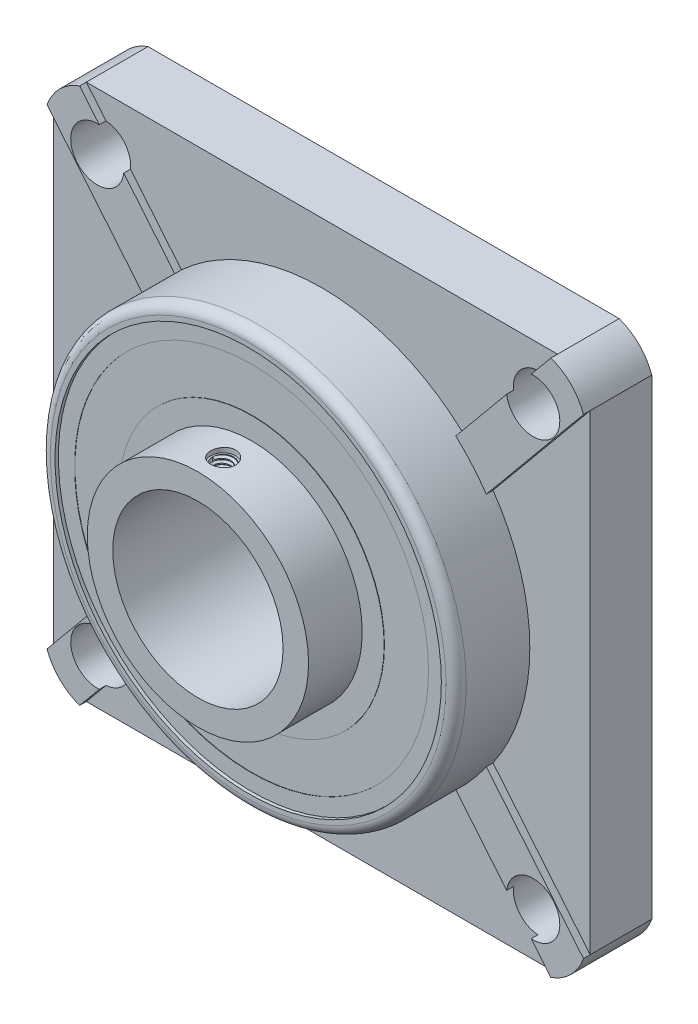
SolidWorks part; units mm, degrees
ref_plane "Alzado" through (0, 0, 0) normal (0, 0, 1) x (1, 0, 0)
ref_plane "Planta" through (0, 0, 0) normal (0, 1, 0) x (1, 0, 0)
ref_plane "Vista lateral" through (0, 0, 0) normal (1, 0, 0) x (0, 0, -1)
sketch "Croquis1" plane through (0, 0, 0) normal (0, 0, 1) x (1, 0, 0)
  line L1 (-80, -80) -> (80, -80)
  line L2 (-80, -80) -> (-80, 80)
  line L3 (-80, 80) -> (80, 80)
  line L4 (80, -80) -> (80, 80)
  line L5 (-80, -80) -> (80, 80) construction
  line L6 (-80, 80) -> (80, -80) construction
  circle A0 centre (0, 0) radius 25.4
  point P0 (0, 0)
  dimension "D3" = 50.8
  dimension "D1" = 160
  dimension "D2" = 160
extrude "Saliente-Extruir1" add sketch "Croquis1" along normal blind 55.372
sketch "Croquis2" plane through (0, 0, 55.372) normal (0, 0, 1) x (1, 0, 0)
  line L0 (0, 0) -> (0, 65) construction
  line L1 (0, 65) -> (65, 65) construction
  line L2 (0, 0) -> (-80, 0) construction
  line L3 (-80, 80) -> (-80, -80) construction
  line L4 (0, -65) -> (65, -65) construction
  circle A0 centre (65, 65) radius 7.9375
  circle A1 centre (-65, 65) radius 7.9375
  circle A2 centre (-65, -65) radius 7.9375
  circle A3 centre (65, -65) radius 7.9375
  dimension "D3" = 15.875
  dimension "D1" = 65
  dimension "D2" = 65
extrude "Cortar-Extruir1" cut sketch "Croquis2" against normal up to surface (55.372 mm away) up to face at (0, 0, 0)
sketch "Croquis3" plane through (0, 0, 55.372) normal (0, 0, 1) x (1, 0, 0)
  line L1 (-95.3572, -94.7038) -> (95.3572, -94.7038)
  line L2 (-95.3572, -94.7038) -> (-95.3572, 94.7038)
  line L3 (-95.3572, 94.7038) -> (95.3572, 94.7038)
  line L4 (95.3572, -94.7038) -> (95.3572, 94.7038)
  line L5 (-95.3572, -94.7038) -> (95.3572, 94.7038) construction
  line L6 (-95.3572, 94.7038) -> (95.3572, -94.7038) construction
  circle A0 centre (0, 0) radius 33
  dimension "D1" = 66
extrude "Cortar-Extruir2" cut sketch "Croquis3" against normal blind 15
sketch "Croquis4" plane through (0, 0, 40.372) normal (0, 0, 1) x (1, 0, 0)
  line L1 (-101.1829, -102.9025) -> (101.1829, -102.9025)
  line L2 (-101.1829, -102.9025) -> (-101.1829, 102.9025)
  line L3 (-101.1829, 102.9025) -> (101.1829, 102.9025)
  line L4 (101.1829, -102.9025) -> (101.1829, 102.9025)
  line L5 (-101.1829, -102.9025) -> (101.1829, 102.9025) construction
  line L6 (-101.1829, 102.9025) -> (101.1829, -102.9025) construction
  circle A0 centre (0, 0) radius 62
  dimension "D1" = 124
extrude "Cortar-Extruir3" cut sketch "Croquis4" against normal blind 20
sketch "Croquis5" plane through (0, 0, 20.372) normal (0, 0, 1) x (1, 0, 0)
  line L0 (-65, 80.899) -> (-65, 94.2394)
  line L1 (-100.1759, -94.2394) -> (-65, -94.2394)
  line L2 (-100.1759, -94.2394) -> (-100.1759, -65)
  line L3 (-100.1759, 94.2394) -> (-65, 94.2394)
  line L4 (100.1759, -94.2394) -> (100.1759, -65)
  line L5 (-100.1759, -94.2394) -> (100.1759, 94.2394) construction
  line L6 (-100.1759, 94.2394) -> (100.1759, -94.2394) construction
  line L7 (-80.899, 65) -> (-100.1759, 65)
  line L8 (65, 80.899) -> (65, 94.2394)
  line L9 (80.899, 65) -> (100.1759, 65)
  line L10 (-80.899, -65) -> (-100.1759, -65)
  line L11 (-65, -80.899) -> (-65, -94.2394)
  line L12 (65, -80.899) -> (65, -94.2394)
  line L13 (80.899, -65) -> (100.1759, -65)
  line L14 (65, -94.2394) -> (100.1759, -94.2394)
  line L15 (100.1759, 65) -> (100.1759, 94.2394)
  line L16 (-100.1759, 65) -> (-100.1759, 94.2394)
  line L17 (65, 94.2394) -> (100.1759, 94.2394)
  arc A0 (-65, 80.899) -> (-80.899, 65) centre (-65, 65) ccw
  arc A1 (80.899, 65) -> (65, 80.899) centre (65, 65) ccw
  arc A2 (-80.899, -65) -> (-65, -80.899) centre (-65, -65) ccw
  arc A3 (65, -80.899) -> (80.899, -65) centre (65, -65) ccw
  point P12 (0, 0)
extrude "Cortar-Extruir4" cut sketch "Croquis5" against normal blind 60
sketch "Croquis6" plane through (0, 0, 20.372) normal (0, 0, 1) x (1, 0, 0)
  line L0 (-70.2705, 80) -> (-41.913, 45.687)
  line L1 (-80, 70.2705) -> (-51.0287, 35.2147)
  line L2 (70.2705, 80) -> (41.913, 45.687)
  line L3 (80, 70.2705) -> (51.0287, 35.2147)
  line L4 (-80, 70.2705) -> (-87.4466, 70.2705)
  line L5 (70.2705, -86.8382) -> (-70.2705, -86.8382)
  line L6 (87.4466, -70.2705) -> (87.4466, 70.2705)
  line L7 (70.2705, 86.8382) -> (-70.2705, 86.8382)
  line L8 (-87.4466, -70.2705) -> (-87.4466, 70.2705)
  line L9 (87.4466, -86.8382) -> (-87.4466, 86.8382) construction
  line L10 (87.4466, 86.8382) -> (-87.4466, -86.8382) construction
  line L11 (-70.2705, 80) -> (-70.2705, 86.8382)
  line L12 (70.2705, 80) -> (70.2705, 86.8382)
  line L13 (80, 70.2705) -> (87.4466, 70.2705)
  line L14 (0, 0) -> (-80, 0) construction
  line L15 (80, -70.2705) -> (51.0287, -35.2147)
  line L16 (-80, -70.2705) -> (-80, 70.2705) construction
  line L17 (-70.2705, -80) -> (-70.2705, -86.8382)
  line L18 (70.2705, -80) -> (41.913, -45.687)
  line L19 (-70.2705, -80) -> (-41.913, -45.687)
  line L20 (-80, -70.2705) -> (-51.0287, -35.2147)
  line L21 (-80, -70.2705) -> (-87.4466, -70.2705)
  line L22 (80, -70.2705) -> (87.4466, -70.2705)
  line L23 (70.2705, -80) -> (70.2705, -86.8382)
  arc A0 (-51.0287, 35.2147) -> (-51.0287, -35.2147) centre (0, 0) ccw
  arc A1 (41.913, 45.687) -> (-41.913, 45.687) centre (0, 0) ccw
  arc A2 (51.0287, -35.2147) -> (51.0287, 35.2147) centre (0, 0) ccw
  arc A3 (-41.913, -45.687) -> (41.913, -45.687) centre (0, 0) ccw
extrude "Cortar-Extruir5" cut sketch "Croquis6" against normal blind 2
fillet "Redondeo1" radius 3 1 edges at (62, 0, 40.372)
sketch "Croquis7" plane through (0, 0, 40.372) normal (0, 0, 1) x (1, 0, 0)
  circle A0 centre (0, 0) radius 57.6092
  circle A1 centre (0, 0) radius 33
extrude "Cortar-Extruir6" cut sketch "Croquis7" against normal blind 1
sketch "Croquis8" plane through (0, 0, 39.372) normal (0, 0, 1) x (1, 0, 0)
  circle A0 centre (0, 0) radius 39.5437
  circle A1 centre (0, 0) radius 52.7758
extrude "Cortar-Extruir7" cut sketch "Croquis8" against normal blind 0.1
sketch "Croquis9" plane through (0, 80, 0) normal (0, 1, 0) x (1, 0, 0)
  line L0 (0, -55.372) -> (0, -40.3314) construction
  line L1 (-33, -55.372) -> (33, -55.372) construction
  circle A0 centre (0, -47.8517) radius 3.175
  dimension "D1" = 6.35
extrude "Cortar-Extruir8" cut sketch "Croquis9" against normal blind 65
sketch "Croquis10" plane through (0, 80, 0) normal (0, 1, 0) x (1, 0, 0)
  circle A0 centre (0, -47.8517) radius 3.704
extrude "Cortar-Extruir9" cut sketch "Croquis10" against normal blind 48.5
thread "Rosca1" pitch 1.27 method extrude profile "Perfil de rosca1" start angle 0, offset 0, length 6, pitch 1.27, diameter 6.35
ref_plane "Plano1" through (-3.175, 31.5, 47.8517) normal (0, 0, 1) x (-1, 0, 0)
sketch "Perfil de rosca1" plane through (-3.175, 31.5, 47.8517) normal (0, 0, 1) x (-1, 0, 0)
  line L0 (0, 0) -> (0, 1.27) construction
  line L11 (0, 0) -> (0, 1.1112)
  line L12 (0, 1.1112) -> (-0.6874, 0.7144)
  line L13 (-0.6874, 0.7144) -> (-0.6874, 0.3969)
  line L15 (-0.6874, 0.3969) -> (0, 0)
  line L17 (-0.6874, 0.5556) -> (0, 0.5556) construction
  point P2 (0, 0)
  dimension "Pitch" = 1.27
  dimension "Profile_Angle" = 60
  dimension "Profile_Land" = 0.3175
  dimension "Profile_Height" = 0.6874
